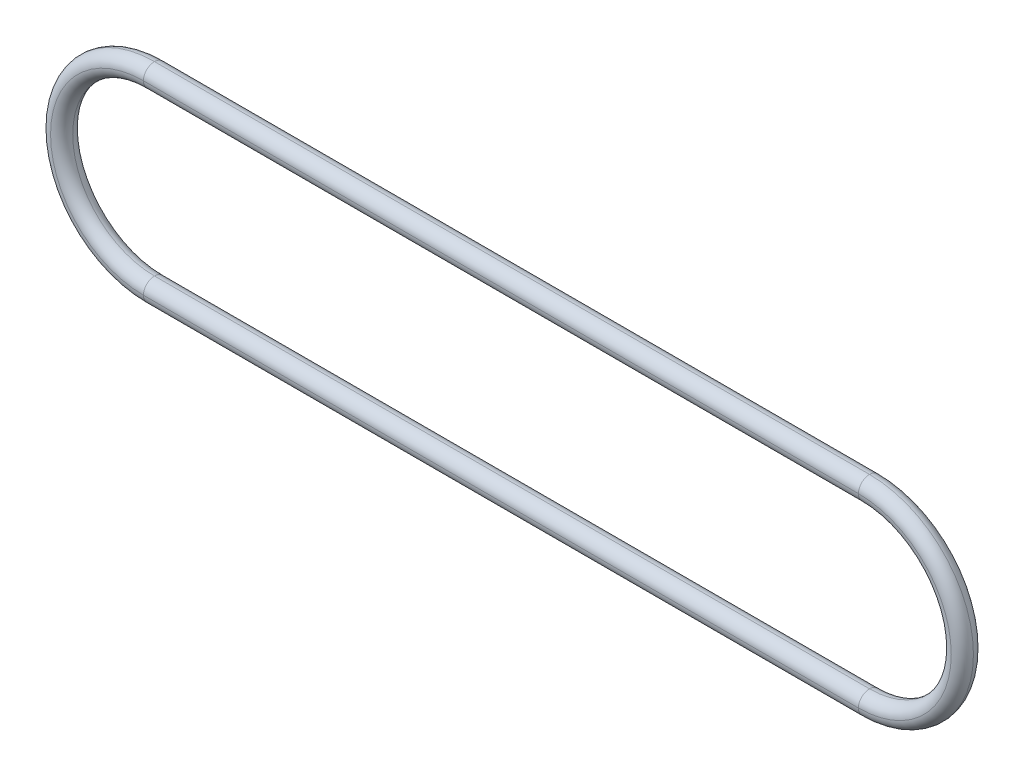
SolidWorks part; units mm, degrees
ref_plane "Plan de face" through (0, 0, 0) normal (0, 0, 1) x (1, 0, 0)
ref_plane "Plan de dessus" through (0, 0, 0) normal (0, 1, 0) x (1, 0, 0)
ref_plane "Plan de droite" through (0, 0, 0) normal (1, 0, 0) x (0, 0, -1)
sketch "Esquisse1" plane through (0, 0, 0) normal (0, 0, 1) x (1, 0, 0)
  line L0 (0, 0) -> (129, 0) construction
  line L1 (0, 14.75) -> (129, 14.75)
  line L2 (0, -14.75) -> (129, -14.75)
  line L3 (0, 0) -> (129, 0) construction
  line L4 (0, 18.75) -> (129, 18.75)
  line L5 (0, -18.75) -> (129, -18.75)
  arc A0 (0, 14.75) -> (0, -14.75) centre (0, 0) ccw
  arc A1 (129, -14.75) -> (129, 14.75) centre (129, 0) ccw
  arc A2 (0, 18.75) -> (0, -18.75) centre (0, 0) ccw
  arc A3 (129, -18.75) -> (129, 18.75) centre (129, 0) ccw
  point P3 (64.5, 0)
  point P10 (64.5, 0)
  dimension "D1" = 14.75
  dimension "D2" = 129
  dimension "D3" = 4
extrude "Boss.-Extru.1" add sketch "Esquisse1" along normal blind 4
fillet "Congé1" radius 2 16 edges at (143.75, 0, 0) (64.5, -14.75, 0) (-14.75, 0, 0) (147.75, 0, 0) (64.5, -18.75, 0) (-18.75, 0, 0) (143.75, 0, 4) (64.5, -14.75, 4) (-14.75, 0, 4) (147.75, 0, 4) (64.5, -18.75, 4) (-18.75, 0, 4) (64.5, 14.75, 0) (64.5, 18.75, 0) (64.5, 14.75, 4) (64.5, 18.75, 4)
